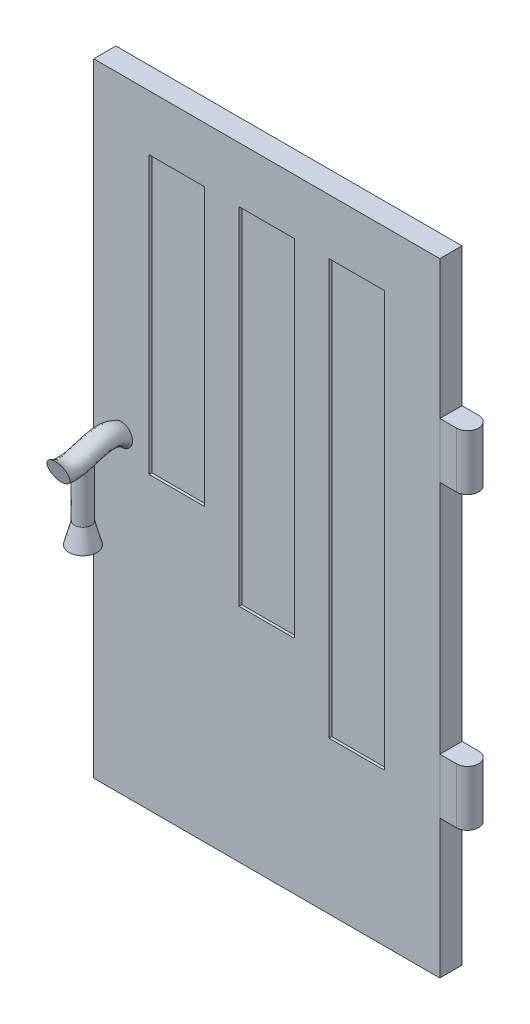
SolidWorks part; units mm, degrees
ref_plane "Alzado" through (0, 0, 0) normal (0, 0, 1) x (1, 0, 0)
ref_plane "Planta" through (0, 0, 0) normal (0, 1, 0) x (1, 0, 0)
ref_plane "Vista lateral" through (0, 0, 0) normal (1, 0, 0) x (0, 0, -1)
sketch "Croquis15" plane through (0, 0, 0) normal (0, 0, 1) x (1, 0, 0)
  line L1 (62.5, -112.5) -> (-62.5, -112.5)
  line L2 (62.5, -112.5) -> (62.5, 112.5)
  line L3 (62.5, 112.5) -> (-62.5, 112.5)
  line L4 (-62.5, -112.5) -> (-62.5, 112.5)
  line L5 (62.5, -112.5) -> (-62.5, 112.5) construction
  line L6 (62.5, 112.5) -> (-62.5, -112.5) construction
  line L15 (72.5, -62.5) -> (62.5, -62.5)
  line L16 (62.5, -42.5) -> (62.5, -62.5)
  point P0 (0, 0)
  point P11 (67.5, -52.5)
  dimension "D1" = 225
  dimension "D2" = 125
  dimension "D3" = 50
extrude "Saliente-Extruir1" add sketch "Croquis15" along normal blind 8 contours L4 L1 L2 L3 | L2 | L2 L3 L4 L1 region at (0, 0, 0)
sketch "Croquis17" plane through (0, 0, 0) normal (0, 0, 1) x (1, 0, 0)
  line L0 (62.5, -112.5) -> (62.5, 112.5) construction
  line L1 (72.5, 62.5) -> (62.5, 62.5)
  line L2 (72.5, 62.5) -> (72.5, 42.5)
  line L3 (72.5, 42.5) -> (62.5, 42.5)
  line L4 (62.5, 62.5) -> (62.5, 42.5)
  line L5 (72.5, 62.5) -> (62.5, 42.5) construction
  line L6 (72.5, 42.5) -> (62.5, 62.5) construction
  line L7 (72.5, -42.5) -> (62.5, -42.5)
  line L8 (72.5, -42.5) -> (72.5, -62.5)
  line L9 (72.5, -62.5) -> (62.5, -62.5)
  line L10 (62.5, -42.5) -> (62.5, -62.5)
  line L11 (72.5, -42.5) -> (62.5, -62.5) construction
  line L12 (72.5, -62.5) -> (62.5, -42.5) construction
  point P0 (67.5, 52.5)
  point P5 (67.5, -52.5)
  dimension "D1" = 50
  dimension "D2" = 20
  dimension "D3" = 10
  dimension "D4" = 10
  dimension "D5" = 20
  dimension "D6" = 50
extrude "Saliente-Extruir3" add sketch "Croquis17" along normal blind 8 separate body
fillet "Redondeo1" 2 edges at (72.5, 52.5, 8) (72.5, 52.5, 0) type full round first side face at (67.5, 52.5, 8) second side face at (67.5, 52.5, 0) middle face at (72.5, 52.5, 4)
fillet "Redondeo2" 2 edges at (72.5, -52.5, 8) (72.5, -52.5, 0) type full round first side face at (67.5, -52.5, 8) second side face at (67.5, -52.5, 0) middle face at (72.5, -52.5, 4)
sketch "Croquis18" plane through (0, -62.5, 0) normal (0, -1, 0) x (1, 0, 0)
  circle A0 centre (68.5, 4) radius 2
  arc A1 (68.5, 0) -> (68.5, 8) centre (68.5, 4) ccw construction
  dimension "D1" = 4
extrude "Cortar-Extruir2" cut sketch "Croquis18" against normal blind 10
sketch "Croquis19" plane through (0, 42.5, 0) normal (0, -1, 0) x (1, 0, 0)
  circle A0 centre (68.5, 4) radius 2
  arc A1 (68.5, 0) -> (68.5, 8) centre (68.5, 4) ccw construction
  dimension "D1" = 4
extrude "Cortar-Extruir3" cut sketch "Croquis19" against normal blind 10
sketch "Croquis20" plane through (0, 0, 8) normal (0, 0, 1) x (1, 0, 0)
  line L0 (-62.5, -112.5) -> (-62.5, 112.5) construction
  line L1 (-42.5, 92.5) -> (-22.5, 92.5)
  line L2 (-42.5, 92.5) -> (-42.5, -7.5)
  line L3 (-42.5, -7.5) -> (-22.5, -7.5)
  line L4 (-22.5, 92.5) -> (-22.5, -7.5)
  line L5 (-42.5, 92.5) -> (-22.5, -7.5) construction
  line L6 (-42.5, -7.5) -> (-22.5, 92.5) construction
  line L7 (62.5, 112.5) -> (-62.5, 112.5) construction
  line L13 (10, -32.5) -> (-10, -32.5)
  line L14 (10, -32.5) -> (10, 92.5)
  line L15 (10, 92.5) -> (-10, 92.5)
  line L16 (-10, -32.5) -> (-10, 92.5)
  line L17 (10, -32.5) -> (-10, 92.5) construction
  line L18 (10, 92.5) -> (-10, -32.5) construction
  line L19 (42.5, 92.5) -> (22.5, 92.5)
  line L20 (42.5, 92.5) -> (42.5, -57.5)
  line L21 (42.5, -57.5) -> (22.5, -57.5)
  line L22 (22.5, 92.5) -> (22.5, -57.5)
  line L23 (42.5, 92.5) -> (22.5, -57.5) construction
  line L24 (42.5, -57.5) -> (22.5, 92.5) construction
  point P0 (-32.5, 42.5)
  point P9 (0, 30)
  point P14 (32.5, 17.5)
  dimension "D1" = 20
  dimension "D2" = 20
  dimension "D3" = 100
  dimension "D4" = 20
  dimension "D5" = 20
  dimension "D6" = 20
  dimension "D7" = 12.5
  dimension "D8" = 125
  dimension "D9" = 12.5
  dimension "D10" = 150
extrude "Cortar-Extruir4" cut sketch "Croquis20" against normal blind 1
sketch "Croquis22" plane through (0, 0, 8) normal (0, 0, 1) x (1, 0, 0)
  line L0 (-62.5, 0) -> (-52.5, 0) construction
  line L1 (-62.5, -112.5) -> (-62.5, 112.5) construction
  circle A0 centre (-52.5, 0) radius 4
  dimension "D2" = 8
  dimension "D1" = 10
ref_plane "Plano3" through (-52.5, 0, 0) normal (-1, 0, 0) x (0, 0, 1)
sketch "Croquis23" plane through (-52.5, 0, 0) normal (-1, 0, 0) x (0, 0, 1)
  spline S0 degree 3 poles (8, 0) (16.008, 5.4945) (22.8157, -2.864) (30.7635, -0.3168) knots 0 0 0 0 1 1 1 1
  point P2 (0, 0)
  point P4 (0, 0)
  point P6 (0, 0)
  point P7 (0, 0)
  point P9 (0, 0)
  point P10 (24.5584, 1.6859)
  point P11 (24.5885, -0.4944)
sketch "Croquis24" plane through (0, 0, 7) normal (0, 0, 1) x (1, 0, 0)
sweep "Barrer1" add profiles "Croquis22" path "Croquis23"
ref_plane "Plano4" through (0, 0, 0) normal (0, 1, 0) x (1, 0, 0)
sketch "Croquis25" plane through (0, 0, 0) normal (0, 1, 0) x (1, 0, 0)
  line L0 (-52.5, -29.6151) -> (-52.5, -35.8294) construction
  circle A0 centre (-52.5, -21.8769) radius 3
  ellipse E0 centre (-52.5, -30.7635) end of major axis (-56.5, -30.7635) minor radius 1.1484 construction
  point P10 (0, 0)
  dimension "D1" = 6
extrude "Saliente-Extruir4" add sketch "Croquis25" against normal blind 20
sketch "Croquis26" plane through (-52.5, 0, 0) normal (-1, 0, 0) x (0, 0, 1)
  line L0 (21.8769, -20) -> (21.8769, -27.5)
  line L1 (18.8769, -20) -> (24.8769, -20) construction
  line L2 (21.8769, -27.5) -> (26.8769, -27.5)
  line L3 (26.8769, -27.5) -> (24.8769, -20)
  line L4 (24.8769, -20) -> (21.8769, -20)
  dimension "D1" = 7.5
  dimension "D2" = 5
revolve "Revolución2" add sketch "Croquis26" angle 360 about L0
